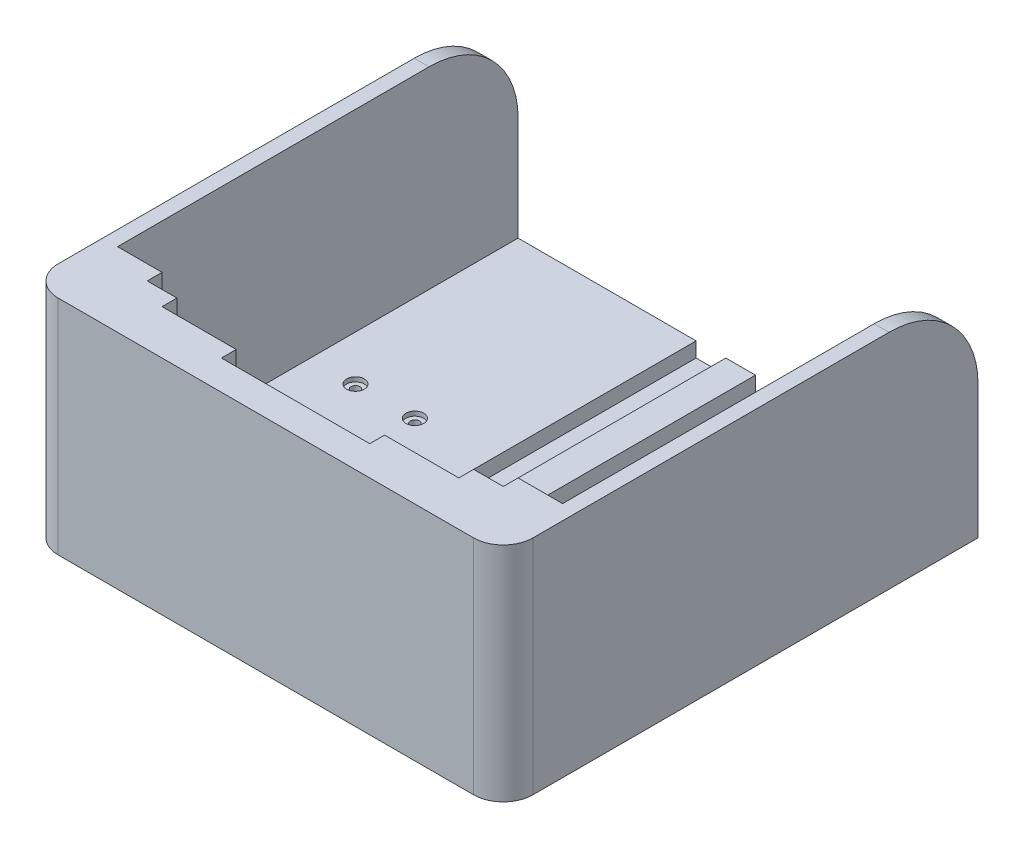
SolidWorks part; units mm, degrees
ref_plane "Front Plane" through (0, 0, 0) normal (0, 0, 1) x (1, 0, 0)
ref_plane "Top Plane" through (0, 0, 0) normal (0, 1, 0) x (1, 0, 0)
ref_plane "Right Plane" through (0, 0, 0) normal (1, 0, 0) x (0, 0, -1)
sketch "Sketch1" plane through (0, 0, 0) normal (0, 1, 0) x (1, 0, 0)
  line L1 (-80, 80) -> (80, 80)
  line L2 (-80, 80) -> (-80, -80)
  line L3 (-80, -80) -> (80, -80)
  line L4 (80, 80) -> (80, -80)
  line L5 (-80, 80) -> (80, -80) construction
  line L6 (-80, -80) -> (80, 80) construction
  point P0 (0, 0)
  dimension "D1" = 160
  dimension "D2" = 160
extrude "Boss-Extrude1" add sketch "Sketch1" along normal blind 75
sketch "Sketch2" plane through (0, 75, 0) normal (0, 1, 0) x (1, 0, 0)
  line L0 (-80, 80) -> (-80, -80) construction
  line L2 (-75, 80) -> (75, 80)
  line L4 (-75, 80) -> (-75, -70)
  line L5 (-75, -70) -> (75, -70)
  line L6 (75, 80) -> (75, -70)
  line L7 (80, -80) -> (80, 80) construction
  line L8 (80, 80) -> (-80, 80) construction
  line L9 (-80, -80) -> (80, -80) construction
  point P6 (0, 0)
  point P13 (0, 0)
  dimension "D1" = 5
  dimension "D2" = 5
  dimension "D3" = 0
  dimension "D4" = 10
extrude "Cut-Extrude1" cut sketch "Sketch2" against normal offset from surface (65 mm away) 10 up to face at (0, 0, 0)
sketch "Sketch3" plane through (0, 0, 70) normal (0, 0, -1) x (-1, 0, 0)
  line L0 (-75, 10) -> (75, 10) construction
  line L1 (-75, 75) -> (-60, 75)
  line L2 (-75, 75) -> (-75, 10)
  line L3 (-75, 10) -> (-60, 10)
  line L4 (-60, 75) -> (-60, 10)
  line L5 (0, 75) -> (0, 10) construction
  line L6 (75, 75) -> (-75, 75) construction
  line L7 (75, 10) -> (60, 10)
  line L8 (60, 75) -> (60, 10)
  line L9 (75, 75) -> (60, 75)
  line L10 (75, 75) -> (75, 10)
  dimension "D1" = 15
extrude "Boss-Extrude2" add sketch "Sketch3" along normal blind 15
sketch "Sketch4" plane through (0, 0, 70) normal (0, 0, -1) x (-1, 0, 0)
  line L0 (0, 75) -> (0, 10) construction
  line L1 (60, 75) -> (-60, 75) construction
  line L2 (75, 10) -> (-75, 10) construction
  line L3 (-60, 10) -> (60, 10) construction
  line L4 (-60, 75) -> (-50, 75)
  line L5 (-60, 75) -> (-60, 10)
  line L6 (-60, 10) -> (-50, 10)
  line L7 (-50, 75) -> (-50, 10)
  line L8 (60, 10) -> (50, 10)
  line L9 (50, 75) -> (50, 10)
  line L10 (60, 75) -> (50, 75)
  line L11 (60, 75) -> (60, 10)
  dimension "D1" = 10
extrude "Boss-Extrude3" add sketch "Sketch4" along normal blind 10
fillet "Fillet1" radius 10 2 edges at (80, 37.5, 80) (-80, 37.5, 80)
sketch "Sketch11" plane through (0, 0, 70) normal (0, 0, -1) x (-1, 0, 0)
  line L0 (-50, 10) -> (50, 10) construction
  line L1 (-50, 75) -> (-25, 75)
  line L2 (-50, 75) -> (-50, 10)
  line L3 (-50, 10) -> (-25, 10)
  line L4 (-25, 75) -> (-25, 10)
  line L5 (0, 75) -> (0, 10) construction
  line L6 (50, 75) -> (-50, 75) construction
  line L7 (75, 10) -> (-75, 10) construction
  line L8 (50, 10) -> (25, 10)
  line L9 (25, 75) -> (25, 10)
  line L10 (50, 75) -> (25, 75)
  line L11 (50, 75) -> (50, 10)
  dimension "D1" = 25
extrude "Boss-Extrude4" add sketch "Sketch11" along normal blind 5
fillet "Fillet2" radius 30 2 edges at (-77.5, 75, -80) (77.5, 75, -80)
sketch "Sketch15" plane through (0, 0, 0) normal (0, -1, 0) x (1, 0, 0)
  line L0 (-80, 0) -> (80, 0) construction
  line L1 (80, 70) -> (80, -80) construction
  line L2 (0, 0) -> (0, 80) construction
  line L3 (-70, 80) -> (70, 80) construction
  circle A0 centre (-59.8059, 10) radius 1.5
  circle A1 centre (-39.8059, 10) radius 1.5
  circle A2 centre (39.8059, 10) radius 1.5
  circle A3 centre (59.8059, 10) radius 1.5
  circle A4 centre (59.8059, -10) radius 1.5
  circle A5 centre (39.8059, -10) radius 1.5
  circle A6 centre (-39.8059, -10) radius 1.5
  circle A7 centre (-59.8059, -10) radius 1.5
  point P6 (0, 0)
  dimension "D1" = 3
  dimension "D2" = 3
  dimension "D3" = 20
  dimension "D4" = 10
extrude "Cut-Extrude2" cut sketch "Sketch15" against normal up to surface (10 mm away) up to face at (0, 10, 43.75)
sketch "Sketch17" plane through (0, 10, 0) normal (0, 1, 0) x (1, 0, 0)
  line L0 (-59.8059, 10) -> (-39.8059, 10) construction
  line L1 (-39.8059, 10) -> (-39.8059, -10) construction
  line L2 (-49.8059, 10) -> (-49.8059, -10) construction
  line L3 (-39.8059, 0) -> (-59.8059, 0) construction
  line L4 (0, 24.5779) -> (0, -24.5779) construction
  circle A1 centre (-59.8059, 10) radius 3
  circle A2 centre (-39.8059, 10) radius 3
  circle A3 centre (-39.8059, -10) radius 3
  circle A4 centre (-59.8059, -10) radius 3
  circle A5 centre (39.8059, -10) radius 3
  circle A6 centre (59.8059, -10) radius 3
  circle A7 centre (39.8059, 10) radius 3
  circle A8 centre (59.8059, 10) radius 3
  point P19 (0, 0)
  dimension "D1" = 6
extrude "Cut-Extrude3" cut sketch "Sketch17" against normal blind 1.5
sketch "Sketch18" plane through (0, 10, 0) normal (0, 1, 0) x (1, 0, 0)
  line L0 (0, 80) -> (0, -70) construction
  line L1 (-75, 80) -> (75, 80) construction
  line L2 (25, -70) -> (-25, -70) construction
  line L3 (-25, -70) -> (25, -70) construction
  line L4 (5, 80) -> (15, 80)
  line L5 (5, 80) -> (5, -65)
  line L6 (5, -65) -> (15, -65)
  line L7 (15, 80) -> (15, -65)
  line L8 (-5, -65) -> (-15, -65)
  line L9 (-15, 80) -> (-15, -65)
  line L10 (-5, 80) -> (-15, 80)
  line L11 (-5, 80) -> (-5, -65)
  dimension "D1" = 10
  dimension "D2" = 0
  dimension "D3" = 10
  dimension "D4" = 5
extrude "Cut-Extrude6" cut sketch "Sketch18" against normal blind 5
